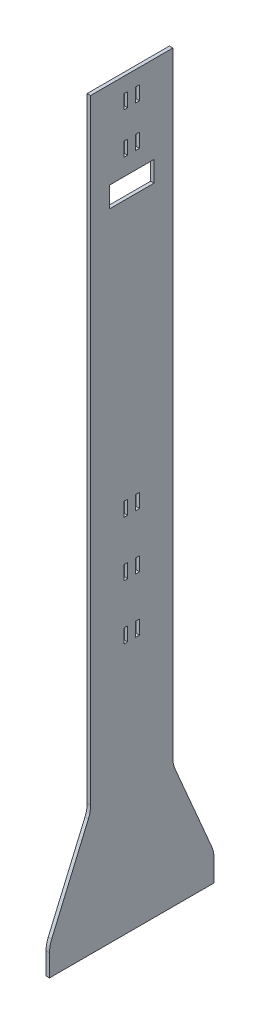
SolidWorks part; units mm, degrees
ref_plane "Front Plane" through (0, 0, 0) normal (0, 0, 1) x (1, 0, 0)
ref_plane "Top Plane" through (0, 0, 0) normal (0, 1, 0) x (1, 0, 0)
ref_plane "Right Plane" through (0, 0, 0) normal (1, 0, 0) x (0, 0, -1)
sketch "Sketch1" plane through (0, 0, 0) normal (1, 0, 0) x (0, 0, -1)
  line L1 (-38.1, 457.2) -> (38.1, 457.2)
  line L2 (-38.1, 457.2) -> (-38.1, -457.2)
  line L3 (-38.1, -457.2) -> (38.1, -457.2)
  line L4 (38.1, 457.2) -> (38.1, -457.2)
  line L5 (-38.1, 457.2) -> (38.1, -457.2) construction
  line L6 (-38.1, -457.2) -> (38.1, 457.2) construction
  point P0 (0, 0)
  dimension "D1" = 914.4
  dimension "D2" = 76.2
extrude "Boss-Extrude1" add sketch "Sketch1" along normal blind 3.175
sketch "Sketch2" plane through (3.175, 0, 0) normal (1, 0, 0) x (0, 0, -1)
  line L0 (-38.1, -457.2) -> (38.1, -457.2) construction
  line L1 (3.722, -204.5335) -> (7.278, -204.5335)
  line L2 (3.722, -204.5335) -> (3.722, -217.4875)
  line L3 (3.722, -217.4875) -> (7.278, -217.4875)
  line L4 (7.278, -204.5335) -> (7.278, -217.4875)
  line L5 (3.722, -204.5335) -> (7.278, -217.4875) construction
  line L6 (3.722, -217.4875) -> (7.278, -204.5335) construction
  point P0 (5.5, -211.0105)
  dimension "D1" = 3.556
  dimension "D2" = 12.954
  dimension "D3" = 239.7125
  dimension "D4" = 3.722
extrude "Cut-Extrude1" cut sketch "Sketch2" against normal through all
mirror "Mirror1" about plane through (0, 0, 0) normal (0, 0, 1) of "Cut-Extrude1"
pattern_linear "LPattern1" count 2 spacing 50.8 along (0, 1, 0) count 2 spacing 50.8 along (0, -1, 0) of "Mirror1"
sketch "Sketch3" plane through (3.175, 0, 0) normal (1, 0, 0) x (0, 0, -1)
  line L0 (7.278, -166.6875) -> (7.278, -153.7335) construction
  line L1 (3.722, 135.1915) -> (7.278, 135.1915)
  line L2 (3.722, 135.1915) -> (3.722, 122.2375)
  line L3 (3.722, 122.2375) -> (7.278, 122.2375)
  line L4 (7.278, 135.1915) -> (7.278, 122.2375)
  line L5 (3.722, 135.1915) -> (7.278, 122.2375) construction
  line L6 (3.722, 122.2375) -> (7.278, 135.1915) construction
  line L7 (7.278, -153.7335) -> (3.722, -153.7335) construction
  line L8 (3.722, -153.7335) -> (3.722, -166.6875) construction
  line L9 (0, 0) -> (0, 52.1648) construction
  line L10 (-3.722, 122.2375) -> (-7.278, 135.1915) construction
  line L11 (-3.722, 135.1915) -> (-7.278, 122.2375) construction
  line L12 (-7.278, 135.1915) -> (-7.278, 122.2375)
  line L13 (-3.722, 122.2375) -> (-7.278, 122.2375)
  line L14 (-3.722, 135.1915) -> (-3.722, 122.2375)
  line L15 (-3.722, 135.1915) -> (-7.278, 135.1915)
  point P0 (5.5, 128.7145)
  point P18 (-5.5, 128.7145)
  dimension "D1" = 275.971
extrude "Cut-Extrude2" cut sketch "Sketch3" against normal through all
pattern_linear "LPattern2" count 2 spacing 38.1 along (0, 1, 0) of "Cut-Extrude2"
sketch "Sketch4" plane through (3.175, 0, 0) normal (1, 0, 0) x (0, 0, -1)
  line L0 (0, -457.2) -> (0, 187.325) construction
  line L1 (-38.1, -457.2) -> (38.1, -457.2) construction
  line L2 (0, 187.325) -> (-38.1, 187.325)
  line L3 (-38.1, 457.2) -> (-38.1, -457.2) construction
  line L4 (-38.1, 187.325) -> (38.1, 187.325)
  line L5 (38.1, -457.2) -> (38.1, 457.2) construction
  line M30 (38.1, -457.2) -> (38.1, 457.2)
  line M31 (38.1, 457.2) -> (-38.1, 457.2)
  line M32 (-38.1, 457.2) -> (-38.1, -457.2)
  dimension "D1" = 644.525
extrude "Cut-Extrude3" cut sketch "Sketch4" against normal through all contours L2 L4 M30 M31 M32 region at (3.175, 322.2625, 0)
sketch "Sketch5" plane through (3.175, 0, 0) normal (1, 0, 0) x (0, 0, -1)
  line L0 (-38.1, -457.2) -> (-38.1, -501.65)
  line L1 (-38.1, -501.65) -> (38.1, -501.65)
  line L2 (38.1, -501.65) -> (38.1, -457.2)
  line L7 (38.1, -457.2) -> (38.1, 187.325)
  line L8 (38.1, 187.325) -> (-38.1, 187.325)
  line L9 (-38.1, 187.325) -> (-38.1, -457.2)
  line L10 (-38.1, -457.2) -> (38.1, -457.2)
  line L14 (-38.1, -457.2) -> (38.1, -457.2)
  dimension "D1" = 44.45
  dimension "D2" = 0
extrude "Boss-Extrude2" add sketch "Sketch5" against normal up to surface (3.175 mm away) up to face at (0, -160.2105, 5.5)
sketch "Sketch6" plane through (3.175, 0, 0) normal (1, 0, 0) x (0, 0, -1)
  line L1 (-20.6375, 106.6318) -> (20.6375, 106.6318)
  line L2 (-20.6375, 106.6318) -> (-20.6375, 87.5818)
  line L4 (20.6375, 106.6318) -> (20.6375, 87.5818)
  line L5 (0, 187.325) -> (0, 38.8722) construction
  line L6 (38.1, 187.325) -> (-38.1, 187.325) construction
  line L7 (-20.6375, 87.5818) -> (20.6375, 87.5818)
  line L8 (-20.9831, 119.3318) -> (20.2919, 119.3318) construction
  point P6 (0, 106.6318)
  dimension "D1" = 19.05
  dimension "D2" = 41.275
  dimension "D3" = 12.7
extrude "Cut-Extrude4" cut sketch "Sketch6" against normal through all contours L7 L4 L1 L2
sketch "Sketch7" plane through (3.175, 0, 0) normal (1, 0, 0) x (0, 0, -1)
  line L0 (-76.2, -501.65) -> (76.2, -501.65)
  line L1 (76.2, -501.65) -> (76.2, -476.25)
  line L2 (76.2, -476.25) -> (38.1, -387.35)
  line L3 (38.1, -501.65) -> (38.1, 187.325) construction
  line L4 (38.1, -387.35) -> (-38.1, -387.35)
  line L5 (-38.1, 187.325) -> (-38.1, -501.65) construction
  line L6 (-38.1, -387.35) -> (-76.2, -476.25)
  line L7 (-76.2, -476.25) -> (-76.2, -501.65)
  line L8 (-38.1, -501.65) -> (38.1, -501.65) construction
  dimension "D1" = 152.4
  dimension "D2" = 38.1
  dimension "D3" = 25.4
  dimension "D4" = 114.3
extrude "Boss-Extrude3" add sketch "Sketch7" against normal blind 3.175
fillet "Fillet1" radius 25.4 4 edges at (1.5875, -476.25, 76.2) (1.5875, -387.35, 38.1) (1.5875, -476.25, -76.2) (1.5875, -387.35, -38.1)
